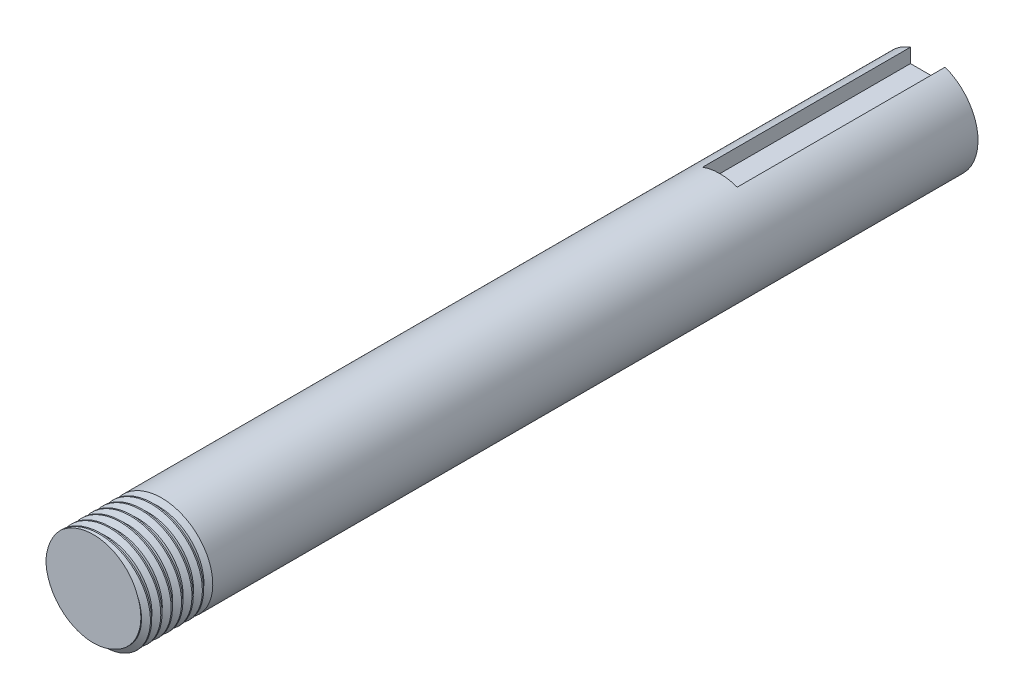
SolidWorks part; units mm, degrees
ref_plane "Front Plane" through (0, 0, 0) normal (0, 0, 1) x (1, 0, 0)
ref_plane "Top Plane" through (0, 0, 0) normal (0, 1, 0) x (1, 0, 0)
ref_plane "Right Plane" through (0, 0, 0) normal (1, 0, 0) x (0, 0, -1)
sketch "Sketch1" plane through (0, 0, 0) normal (0, 0, 1) x (1, 0, 0)
  circle A0 centre (0, 0) radius 7.25
  dimension "D1" = 14.5
extrude "Boss-Extrude1" add sketch "Sketch1" along normal mid plane 120
thread "Thread1" pitch 1.5 method cut profile "Thread Profile1" start angle 0, offset 1.5, length 10, pitch 1.5, diameter 14.5
ref_plane "Plane1" through (-7.25, 0, 61.5) normal (0, -1, 0) x (-1, 0, 0)
sketch "Thread Profile1" plane through (-7.25, 0, 61.5) normal (0, -1, 0) x (-1, 0, 0)
  line L0 (0, 0) -> (0, 1.5) construction
  line L11 (0, 0) -> (0, 1.3125)
  line L12 (0, 1.3125) -> (-0.8119, 0.8437)
  line L13 (-0.8119, 0.8437) -> (-0.8119, 0.4687)
  line L15 (-0.8119, 0.4687) -> (0, 0)
  line L17 (-0.8119, 0.6562) -> (0, 0.6562) construction
  point P2 (0, 0)
  dimension "Pitch" = 1.5
  dimension "Profile_Angle" = 60
  dimension "Profile_Land" = 0.375
  dimension "Profile_Height" = 0.8119
sketch "Sketch2" plane through (0, 0, -60) normal (0, 0, -1) x (-1, 0, 0)
  line L1 (-2.5, 9.75) -> (2.5, 9.75)
  line L2 (-2.5, 9.75) -> (-2.5, 4.75)
  line L3 (-2.5, 4.75) -> (2.5, 4.75)
  line L4 (2.5, 9.75) -> (2.5, 4.75)
  line L5 (-2.5, 9.75) -> (2.5, 4.75) construction
  line L6 (-2.5, 4.75) -> (2.5, 9.75) construction
  circle A0 centre (0, 0) radius 7.25 construction
  point P0 (0, 7.25)
extrude "Cut-Extrude1" cut sketch "Sketch2" against normal blind 30
